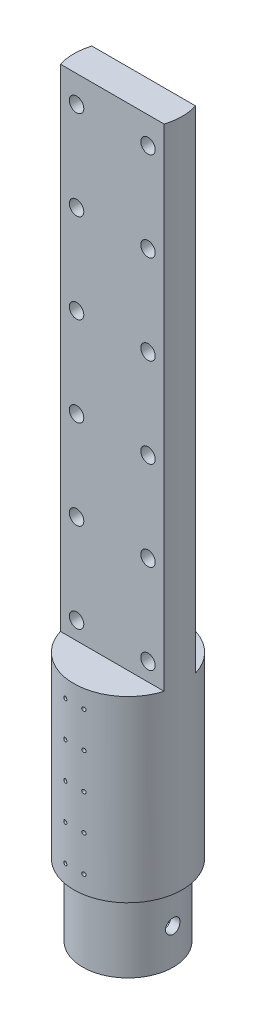
SolidWorks part; units mm, degrees
ref_plane "Front Plane" through (0, 0, 0) normal (0, 0, 1) x (1, 0, 0)
ref_plane "Top Plane" through (0, 0, 0) normal (0, 1, 0) x (1, 0, 0)
ref_plane "Right Plane" through (0, 0, 0) normal (1, 0, 0) x (0, 0, -1)
sketch "Sketch1" plane through (0, 0, 0) normal (0, 1, 0) x (1, 0, 0)
  circle A0 centre (0, 0) radius 25.35
  circle A1 centre (0, 0) radius 30.35
  circle A2 centre (0, 0) radius 20.35
  dimension "D1" = 50.7
  dimension "D2" = 60.7
  dimension "D3" = 5
extrude "Boss-Extrude2" add sketch "Sketch1" along normal blind 375 contours A1 A0 | A0 A2 | A2 region at (-24.633, 0, 0) region at (-29.4916, 0, 0) region at (0, 0, 0)
extrude "Boss-Extrude3" add sketch "Sketch1<3>" against normal blind 40 contours A0 A2 region at (-24.633, 0, 0)
sketch "Sketch1<3>" plane through (0, 0, 0) normal (0, 1, 0) x (1, 0, 0) same geometry as "Sketch1"
sketch "Sketch6" plane through (0, 375, 0) normal (0, 1, 0) x (1, 0, 0)
  line L0 (0, 0) -> (0, -30.35)
  line L1 (0, -37.35) -> (25, -37.35)
  line L2 (0, -37.35) -> (-25, -37.35)
  line L3 (-25, -37.35) -> (-25, -17.35)
  line L4 (-25, -17.35) -> (0, -17.35)
  line L5 (25, -37.35) -> (25, -17.35)
  line L6 (25, -17.35) -> (0, -17.35)
  line L7 (0, -17.35) -> (0.1122, -17.35)
  line L8 (0, 17.35) -> (0.1122, 17.35)
  line L9 (25, 17.35) -> (0, 17.35)
  line L10 (25, 37.35) -> (25, 17.35)
  line L11 (-25, 17.35) -> (0, 17.35)
  line L12 (-25, 37.35) -> (-25, 17.35)
  line L13 (0, 37.35) -> (-25, 37.35)
  line L14 (0, 37.35) -> (25, 37.35)
  line L15 (-46.2124, 0) -> (46.2124, 0)
  line L16 (25, -17.35) -> (42.8318, -17.35)
  line L17 (42.8318, -17.35) -> (-42.8318, -17.35)
  line L18 (25, 17.35) -> (42.8318, 17.35)
  line L19 (-25, 17.35) -> (-42.8318, 17.35)
  line L20 (29.0462, -8.8) -> (-29.0462, -8.8)
  line L21 (29.0462, 8.8) -> (-29.0462, 8.8)
  circle A0 centre (0, 0) radius 30.35
  circle A1 centre (0, -33.85) radius 3.5
  circle A2 centre (0, 33.85) radius 3.5
  circle A4 centre (0, 0) radius 46.2124
  circle M28 centre (0, 0) radius 30.35
  dimension "D1" = 60.7
  dimension "D2" = 7
  dimension "D3" = 25
  dimension "D4" = 25
  dimension "D5" = 20
  dimension "D6" = 8.55
  dimension "D7" = 8.55
extrude "Cut-Extrude3" cut sketch "Sketch6" against normal blind 275 contours A0 L5 L1 L2 L3 L17 | A1 L1 L5 A0 | L0 A0 L5 L6 | L3 A0 L0 L4 | A1 A0 L3 L2 | L10 A0 L12 L11 L8 L9 | A0 L18 L19 L12 L13 L14 L10 | L14 A2 A0 L10 | A0 A2 L13 L12 | L5 A0 L16 | L17 A0 L3 | L20 L0 L6 L16 M28 | L21 L18 L9 L8 L11 L19 M28 | L0 L20 L4 M28 | A1 | A2 region at (9.6779, 375, 22.6591) region at (-13.652, 375, 12.9673) region at (-9.6779, 375, 22.6591) region at (13.652, 375, 12.9673) region at (-15.8636, 375, 31.0586) region at (15.8636, 375, 31.0586) region at (12.5, 375, 38.254) region at (0, 375, -12.9673) region at (33.9159, 375, -18.254) region at (15.8636, 375, -31.0586) region at (0, 375, -22.6591) region at (-15.8636, 375, -31.0586)
ref_plane "Plane1" through (0, 0, 30.35) normal (0, 0, 1) x (1, 0, 0)
sketch "Sketch8" plane through (0, 0, 30.35) normal (0, 0, 1) x (1, 0, 0)
  line L0 (0, 0) -> (0, 100)
  line L1 (29.0462, 100) -> (-29.0462, 100) construction
  line L2 (0, 50) -> (30.35, 50)
  line L3 (30.35, 0) -> (30.35, 375) construction
  line L4 (30.35, 50) -> (-30.35, 50)
  line L5 (-30.35, 375) -> (-30.35, 0) construction
  line L6 (5.215, 50) -> (0, 50)
  line L7 (0, 50) -> (-5.215, 50)
  circle A0 centre (5.215, 50) radius 1.05
  circle A1 centre (-5.215, 50) radius 1.05
  circle A2 centre (-5.215, 70) radius 1.05
  circle A3 centre (5.215, 70) radius 1.05
  circle A4 centre (-5.215, 90) radius 1.05
  circle A5 centre (5.215, 90) radius 1.05
  circle A6 centre (5.215, 30) radius 1.05
  circle A7 centre (-5.215, 30) radius 1.05
  circle A8 centre (5.215, 10) radius 1.05
  circle A9 centre (-5.215, 10) radius 1.05
  dimension "D5" = 3
  dimension "D6" = 3
  dimension "D3" = 2.1
  dimension "D4" = 2.1
  dimension "D1" = 5.215
  dimension "D2" = 5.215
extrude "Cut-Extrude5" cut sketch "Sketch8" against normal blind 137 contours A6 | A7 | A9 | A8 | A0 | A1 | A2 | A3 | A4 | A5
sketch "Sketch9" plane through (0, 0, 0) normal (1, 0, 0) x (0, 0, -1)
  line L0 (25.35, -20) -> (-25.35, -20)
  line L1 (25.35, -40) -> (25.35, 0) construction
  line L2 (-25.35, 0) -> (-25.35, -40) construction
  circle A0 centre (0, -20) radius 4.05
  dimension "D1" = 8.1
extrude "Cut-Extrude6" cut sketch "Sketch9" against normal blind 137 and the other way blind 137 contours A0
sketch "Sketch10" plane through (0, 0, -8.8) normal (0, 0, -1) x (-1, 0, 0)
  line L0 (0, 110) -> (0, 100)
  line L1 (-20, 110) -> (20, 110)
  line L3 (-29.0462, 100) -> (29.0462, 100) construction
  line L4 (29.0462, 100) -> (-29.0462, 100)
  circle A0 centre (-20, 110) radius 4.05
  circle A1 centre (20, 110) radius 4.05
  circle A2 centre (-20, 160) radius 4.05
  circle A3 centre (20, 160) radius 4.05
  circle A4 centre (-20, 210) radius 4.05
  circle A5 centre (20, 210) radius 4.05
  circle A6 centre (-20, 260) radius 4.05
  circle A7 centre (20, 260) radius 4.05
  circle A8 centre (-20, 310) radius 4.05
  circle A9 centre (20, 310) radius 4.05
  circle A10 centre (-20, 360) radius 4.05
  circle A11 centre (20, 360) radius 4.05
  point P6 (0, 100)
  dimension "D2" = 8.1
  dimension "D3" = 8.1
  dimension "D1" = 40
  dimension "D4" = 10
  dimension "D5" = 5
  dimension "D6" = 2
extrude "Cut-Extrude7" cut sketch "Sketch10" against normal blind 137 contours A0 | A1 | A6 | A2 | A4 | A3 | A5 | A7 | A9 | A8 | A11 | A10
